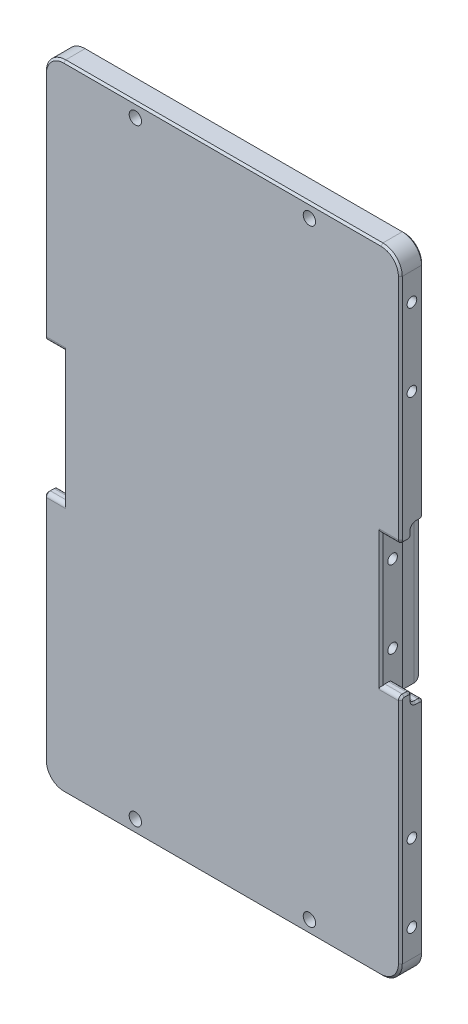
SolidWorks part; units mm, degrees
material "6061 合金"
ref_plane "前视基准面" through (0, 0, 0) normal (0, 0, 1) x (1, 0, 0)
ref_plane "上视基准面" through (0, 0, 0) normal (0, 1, 0) x (1, 0, 0)
ref_plane "右视基准面" through (0, 0, 0) normal (1, 0, 0) x (0, 0, -1)
other "Configuration Table"
sketch "草图1" plane through (0, 0, 0) normal (0, 0, 1) x (1, 0, 0)
  line L1 (-46, -82) -> (46, -82)
  line L2 (-46, -82) -> (-46, 82)
  line L3 (-46, 82) -> (46, 82)
  line L4 (46, -82) -> (46, 82)
  line L5 (-46, -82) -> (46, 82) construction
  line L6 (-46, 82) -> (46, -82) construction
  point P0 (0, 0)
  dimension "D1" = 92
  dimension "D2" = 164
extrude "凸台-拉伸1" add sketch "草图1" along normal mid plane 6
sketch "草图3" plane through (0, 0, 3) normal (0, 0, 1) x (1, 0, 0)
  line L0 (0, 82) -> (0, -82) construction
  line L1 (46, 82) -> (-46, 82) construction
  line L2 (-46, -82) -> (46, -82) construction
  line L8 (-46, 82) -> (-46, -82) construction
  line L9 (-41, -14) -> (-46, -14)
  line L10 (-41, -14) -> (-41, 14)
  line L15 (-41, 14) -> (-46, 14)
  line L21 (-46, -14) -> (-46, 14)
  line L22 (-43.5, 14) -> (-43.5, -14) construction
  line L27 (-41, 0) -> (-46, 0) construction
  line L28 (41, 14) -> (46, 14)
  line L29 (46, -14) -> (46, 14)
  line L30 (41, -14) -> (46, -14)
  line L47 (41, -14) -> (41, 14)
  point P6 (-43.5, 0)
  point P12 (0, 0)
  dimension "D1" = 28
  dimension "D2" = 5
sketch "草图97" plane through (-46, 0, 0) normal (-1, 0, 0) x (0, 0, 1)
  line L1 (0, -20.05) -> (-3, -20.05)
  line L2 (0, -20.05) -> (0, 20.05)
  line L3 (0, 20.05) -> (-3, 20.05)
  line L4 (-3, -20.05) -> (-3, 20.05)
  line L5 (-1.5, 20.05) -> (-1.5, -20.05) construction
  line L6 (0, 0) -> (-3, 0) construction
  line L8 (3, -17) -> (0, -17)
  line L9 (3, -17) -> (3, 17)
  line L10 (3, 17) -> (0, 17)
  line L11 (0, -17) -> (0, 17)
  line L12 (1.5, 17) -> (1.5, -18.4583) construction
  line L13 (3, 0) -> (0, 0) construction
  line L14 (-3, 82) -> (-3, -82) construction
  point P0 (-1.5, 0)
  point P6 (1.5, 0)
  line M2 (-3, 82) -> (-3, -82)
  line M4 (3, -82) -> (3, 82)
  dimension "D1" = 34
  dimension "D2" = 3
  dimension "D3" = 40.1
extrude "切除-拉伸1" cut sketch "草图97" against normal blind 5 contours L2 L3 L1 M2 | L10 L2 L8 M4
sketch "草图98" plane through (-41, 0, 0) normal (-1, 0, 0) x (0, 0, 1)
  line L0 (0, -10) -> (0, 10)
  line L1 (-3, 0) -> (0, 0)
  line L2 (-3, 20.05) -> (-3, -20.05) construction
  point P3 (0, 0)
  dimension "D1" = 20
  dimension "D3" = 3
hole_wizard "M3 螺纹孔1" positions "草图99" profile "草图100" tap size "M3" standard "GB"
sketch "草图99" plane through (-41, 0, 0) normal (-1, 0, 0) x (0, 0, 1)
  point P0 (0, 10)
  point P3 (0, -10)
sketch "草图100" plane through (-41, 10, 0) normal (0, 1, 0) x (0, 0, 1)
  line L0 (0, 0) -> (0, 7.5)
  line L1 (0, 7.5) -> (1.25, 6.7489)
  line L2 (1.25, 6.7489) -> (1.25, 0)
  line L5 (1.25, 0) -> (0, 0)
  line L10 (0, 7.5) -> (-1.25, 6.7489) construction
  line L11 (0, -6.35) -> (0, 107.95) construction
  dimension "螺纹孔钻头直径" = 2.5
  dimension "螺纹孔钻头深度" = 7.5
  dimension "导头角度" = 118
cosmetic thread "孔螺蚊线1" parameters "D1"=6, "D2"=3
cosmetic thread "孔螺蚊线2" parameters "D1"=6, "D2"=3
mirror "镜向1" about plane through (0, 0, 0) normal (1, 0, 0) of "M3 螺纹孔1", "切除-拉伸1"
sketch "草图101" plane through (0, 0, 3) normal (0, 0, -1) x (-1, 0, 0)
  line L0 (-19.2, 0) -> (19.2, 0)
  point P4 (0, 0)
  dimension "D1" = 38.4
hole_wizard "M4 六角凹锥坑螺钉的锥形沉头孔1" [suppressed] positions "草图101" profile "草图103" countersink size "M4" standard "ISO"
sketch "草图103" plane through (-19.2, 0, 3) normal (1, 0, 0) x (0, -1, 0)
  line L0 (0, 0) -> (0, 7.5)
  line L1 (0, 7.5) -> (2.25, 6.1481)
  line L2 (2.25, 6.1481) -> (2.25, 2.23)
  line L3 (2.25, 2.23) -> (4.48, 0)
  line L5 (4.48, 0) -> (0, 0)
  line L6 (-2.25, 2.23) -> (-4.48, 0) construction
  line L10 (0, 7.5) -> (-2.25, 6.1481) construction
  line L11 (0, -6.35) -> (0, 107.95) construction
  dimension "孔直径" = 4.5
  dimension "孔深度" = 7.5
  dimension "近端锥形沉头孔直径" = 8.96
  dimension "近端锥形沉头孔角度" = 90
  dimension "导头角度" = 118
sketch "草图104" plane through (0, 0, -3) normal (0, 0, 1) x (1, 0, 0)
  line L1 (-18, -16) -> (18, -16)
  line L2 (-18, -16) -> (-18, 16)
  line L3 (-18, 16) -> (18, 16)
  line L4 (18, -16) -> (18, 16)
  line L5 (0, 16) -> (0, -16) construction
  line L6 (-18, 0) -> (18, 0) construction
  point P0 (0, 0)
  dimension "D1" = 32
  dimension "D2" = 36
hole_wizard "Ø3.0mm 暗销孔1" [suppressed] positions "草图104" profile "草图106" hole size "Ø3.0" standard "ISO"
sketch "草图106" plane through (18, -16, -3) normal (1, 0, 0) x (0, 1, 0)
  line L0 (0, 0) -> (0, 4.4013)
  line L1 (0, 4.4013) -> (1.5, 3.5)
  line L2 (1.5, 3.5) -> (1.5, 0)
  line L5 (1.5, 0) -> (0, 0)
  line L10 (0, 4.4013) -> (-1.5, 3.5) construction
  line L11 (0, -6.35) -> (0, 107.95) construction
  dimension "孔直径" = 3
  dimension "孔深度" = 3.5
  dimension "导头角度" = 118
sketch "草图107" plane through (0, 0, 3) normal (0, 0, 1) x (1, 0, 0)
  line L0 (-7.5, 0) -> (7.5, 0)
  point P3 (0, 0)
  dimension "D1" = 15
hole_wizard "M4 螺纹孔1" [suppressed] positions "草图107" profile "草图109" tap size "M4" standard "ISO"
sketch "草图109" plane through (7.5, 0, 3) normal (1, 0, 0) x (0, -1, 0)
  line L0 (0, 0) -> (0, 10.1)
  line L1 (0, 10.1) -> (1.65, 9.1086)
  line L2 (1.65, 9.1086) -> (1.65, 0)
  line L5 (1.65, 0) -> (0, 0)
  line L10 (0, 10.1) -> (-1.65, 9.1086) construction
  line L11 (0, -6.35) -> (0, 107.95) construction
  dimension "螺纹孔钻头直径" = 3.3
  dimension "螺纹孔钻头深度" = 10.1
  dimension "导头角度" = 118
cosmetic thread "孔螺蚊线3" [suppressed] parameters "D1"=8, "D2"=4
cosmetic thread "孔螺蚊线4" [suppressed] parameters "D1"=8, "D2"=4
pattern_linear "阵列(线性)1" [suppressed] count 5 spacing 15 count 5 spacing 15
sketch "草图110" plane through (0, 0, 3) normal (0, 0, 1) x (1, 0, 0)
  line L0 (-46, 82) -> (-46, 17) construction
  line L1 (-4.25, -75) -> (4.25, -75) construction
  line L2 (-4.25, -75) -> (-4.25, 75) construction
  line L3 (-4.25, 75) -> (4.25, 75) construction
  line L4 (4.25, -75) -> (4.25, 75) construction
  line L5 (0, 75) -> (0, -75) construction
  line L6 (-4.25, 0) -> (4.25, 0) construction
  line L7 (-41, 75) -> (-11.75, 75)
  line L8 (-41, 75) -> (-41, 25)
  line L9 (-41, 25) -> (-11.75, 25)
  line L10 (-11.75, 75) -> (-11.75, 25)
  line L11 (-41, 75) -> (-11.75, 25) construction
  line L12 (-41, 25) -> (-11.75, 75) construction
  line L13 (46, 82) -> (-46, 82) construction
  line L14 (-91.2198, 0) -> (74.6821, 0) construction
  line L15 (41, 25) -> (11.75, 25)
  line L16 (11.75, 75) -> (11.75, 25)
  line L17 (41, 75) -> (11.75, 75)
  line L18 (41, 75) -> (41, 25)
  line L19 (41, -75) -> (41, -25)
  line L20 (41, -75) -> (11.75, -75)
  line L21 (11.75, -75) -> (11.75, -25)
  line L22 (41, -25) -> (11.75, -25)
  line L23 (-41, -25) -> (-11.75, -25)
  line L24 (-11.75, -75) -> (-11.75, -25)
  line L25 (-41, -75) -> (-11.75, -75)
  line L26 (-41, -75) -> (-41, -25)
  line L27 (32, -18) -> (24.25, -18)
  line L28 (-32, 18) -> (-24.25, 18)
  line L29 (-32, 18) -> (-32, -18)
  line L30 (-32, -18) -> (-24.25, -18)
  line L31 (-24.25, 18) -> (-24.25, -18)
  line L32 (-28.125, -18) -> (-28.125, 18) construction
  line L33 (-32, 0) -> (-24.25, 0) construction
  line L34 (24.25, 18) -> (24.25, -18)
  line L35 (32, 18) -> (24.25, 18)
  line L36 (32, 18) -> (32, -18)
  point P0 (0, 0)
  point P11 (-26.375, 50)
  point P30 (-28.125, 0)
  dimension "D1" = 8.5
  dimension "D2" = 7
  dimension "D3" = 5
  dimension "D4" = 7
  dimension "D5" = 7.5
  dimension "D6" = 25
  dimension "D7" = 7
  dimension "D8" = 32
  dimension "D9" = 20
extrude "切除-拉伸2" [suppressed] cut sketch "草图110" against normal blind 57
sketch "草图112" plane through (-46, 0, 0) normal (-1, 0, 0) x (0, 0, 1)
  line L0 (0, 70) -> (0, -70)
  line L1 (0, 50) -> (0, -50)
  point P1 (0, -70)
  point P2 (0, 70)
  point P7 (0, -50)
  point P20 (0, 50)
  point P25 (0, 0)
  dimension "D1" = 140
  dimension "D2" = 100
sketch "草图111" plane through (0, 0, -3) normal (0, 0, -1) x (-1, 0, 0)
  line L1 (-7.9, -49) -> (7.9, -49)
  line L2 (-7.9, -49) -> (-7.9, -57)
  line L3 (-7.9, -57) -> (7.9, -57)
  line L4 (7.9, -49) -> (7.9, -57)
  line L5 (0, -57) -> (0, -49) construction
  line L6 (-7.9, -53) -> (7.9, -53) construction
  point P0 (0, -53)
  point P4 (0, 0)
  dimension "D1" = 8
  dimension "D2" = 15.8
  dimension "D3" = 53
extrude "切除-拉伸3" [suppressed] cut sketch "草图111" against normal blind 10
fillet "圆角4" [suppressed] radius 0.5
fillet "圆角6" [suppressed] radius 1
fillet "圆角7" [suppressed] radius 2
hole_wizard "M3 螺纹孔2" positions "草图112" profile "草图113" tap size "M3" standard "ISO"
sketch "草图113" plane through (-46, -70, 0) normal (0, 1, 0) x (0, 0, 1)
  line L0 (0, 0) -> (0, 7.5)
  line L1 (0, 7.5) -> (1.25, 6.7489)
  line L2 (1.25, 6.7489) -> (1.25, 0)
  line L5 (1.25, 0) -> (0, 0)
  line L10 (0, 7.5) -> (-1.25, 6.7489) construction
  line L11 (0, -6.35) -> (0, 107.95) construction
  dimension "螺纹孔钻头直径" = 2.5
  dimension "螺纹孔钻头深度" = 7.5
  dimension "导头角度" = 118
cosmetic thread "孔螺蚊线5" parameters "D1"=6, "D2"=3
cosmetic thread "孔螺蚊线6" parameters "D1"=6, "D2"=3
cosmetic thread "孔螺蚊线8" parameters "D1"=6, "D2"=3
cosmetic thread "孔螺蚊线9" parameters "D1"=6, "D2"=3
mirror "镜向2" about plane through (0, 0, 0) normal (1, 0, 0) of "M3 螺纹孔2"
fillet "圆角1" [suppressed] radius 3
fillet "圆角2" [suppressed] radius 2
fillet "圆角3" radius 5 4 edges at (46, -82, 0) (-46, -82, 0) (-46, 82, 0) (46, 82, 0)
fillet "圆角5" radius 1 16 edges at (-43.5, -17, 0) (-43.5, -20.05, 0) (-43.5, -20.05, -3) (-43.5, 20.05, -3) (-43.5, 20.05, 0) (-43.5, 17, 0) (-43.5, 17, 3) (-43.5, -17, 3) (43.5, -20.05, 0) (43.5, -17, 0) (43.5, -17, 3) (43.5, 17, 3) (43.5, 17, 0) (43.5, 20.05, 0) (43.5, 20.05, -3) (43.5, -20.05, -3)
sketch "草图114" [suppressed] plane through (0, 0, -3) normal (0, 0, -1) x (-1, 0, 0)
  line L1 (-41, -68.5) -> (-11.75, -68.5)
  line L2 (-41, -68.5) -> (-41, -88.5)
  line L3 (-41, -88.5) -> (-11.75, -88.5)
  line L4 (-11.75, -68.5) -> (-11.75, -88.5)
  line L5 (-41, -68.5) -> (-11.75, -88.5) construction
  line L6 (-41, -88.5) -> (-11.75, -68.5) construction
  line L11 (-11.75, -75) -> (-11.75, -25) construction
  line L12 (-41, -25) -> (-41, -75) construction
  line L13 (-26.375, -75) -> (-26.375, -82) construction
  line L14 (-41, -75) -> (-11.75, -75) construction
  line L15 (41, -82) -> (-41, -82) construction
  point P4 (-26.375, -78.5)
  dimension "D1" = 20
extrude "切除-拉伸4" [suppressed] cut sketch "草图114" against normal blind 2
sketch "草图115" [suppressed] plane through (0, 0, -1) normal (0, 0, -1) x (-1, 0, 0)
  line L0 (-41, -82) -> (-11.75, -82) construction
  point P0 (-22.5, -78.5)
  point P1 (0, 0)
  dimension "D1" = 22.5
  dimension "D2" = 3.5
hole_wizard "M3 螺纹孔3" [suppressed] positions "草图115" profile "草图116" tap size "M3" standard "ISO"
sketch "草图116" plane through (22.5, -78.5, -1) normal (1, 0, 0) x (0, 1, 0)
  line L0 (0, 0) -> (0, 7.5)
  line L1 (0, 7.5) -> (1.25, 6.7489)
  line L2 (1.25, 6.7489) -> (1.25, 0)
  line L5 (1.25, 0) -> (0, 0)
  line L10 (0, 7.5) -> (-1.25, 6.7489) construction
  line L11 (0, -6.35) -> (0, 107.95) construction
  dimension "螺纹孔钻头直径" = 2.5
  dimension "螺纹孔钻头深度" = 7.5
  dimension "导头角度" = 118
cosmetic thread "孔螺蚊线10" [suppressed] parameters "D1"=6, "D2"=3
cosmetic thread "孔螺纹线1" [suppressed] parameters "D1"=6, "D2"=3
mirror "镜向6" [suppressed] about plane through (0, 0, 0) normal (0, 1, 0)
fillet "圆角8" [suppressed] radius 1
sketch "草图117" plane through (0, 0, -3) normal (0, 0, -1) x (-1, 0, 0)
  line L1 (-12.4, 12.4) -> (12.4, 12.4)
  line L2 (-12.4, 12.4) -> (-12.4, -12.4)
  line L3 (-12.4, -12.4) -> (12.4, -12.4)
  line L4 (12.4, 12.4) -> (12.4, -12.4)
  line L5 (0, -12.4) -> (0, 12.4) construction
  line L6 (-12.4, 0) -> (12.4, 0) construction
  point P0 (0, 0)
  dimension "D1" = 24.8
extrude "切除-拉伸5" [suppressed] cut sketch "草图117" against normal blind 10
fillet "圆角9" [suppressed] radius 1
chamfer "倒角1" [suppressed] distance 0.5 angle 45
chamfer "倒角2" distance 0.5 angle 45 52 edges at (-41, 0, 3) (-46, 47.5, 3) (-44.5355, 80.5355, 3) (0, 82, 3) (44.5355, 80.5355, 3) (46, 47.5, 3) (41, 0, 3) (-46, -47.5, 3) (-44.5355, -80.5355, 3) (0, -82, 3) (44.5355, -80.5355, 3) (46, -47.5, 3) (41, 0, -3) (46, 17.2929, 2.7071) (-46, 17.2929, 2.7071) (46, 17, 1.5) (-46, 17, 1.5) (46, 17.2929, 0.2929) (-46, 17.2929, 0.2929) (46, 18.525, 0) (-46, -18.525, 0) (46, 19.7571, -0.2929) (-46, 19.7571, -0.2929) (46, 20.05, -1.5) (-46, 20.05, -1.5) (46, 20.3429, -2.7071) (-46, 20.3429, -2.7071) (46, 49.025, -3) (44.5355, 80.5355, -3) (0, 82, -3) (-44.5355, 80.5355, -3) (-46, 49.025, -3) (-41, 0, -3) (46, -17.2929, 2.7071) (-46, -17.2929, 2.7071) (46, -17, 1.5) (-46, -17, 1.5) (46, -17.2929, 0.2929) (-46, -17.2929, 0.2929) (46, -18.525, 0) (-46, 18.525, 0) (46, -19.7571, -0.2929) (-46, -19.7571, -0.2929) (46, -20.05, -1.5) (-46, -20.05, -1.5) (46, -20.3429, -2.7071) (-46, -20.3429, -2.7071) (46, -49.025, -3) (-46, -49.025, -3) (-44.5355, -80.5355, -3) (0, -82, -3) (44.5355, -80.5355, -3)
sketch "草图119" plane through (0, 0, -3) normal (0, 0, -1) x (-1, 0, 0)
  line L0 (-41, 0) -> (41, 0) construction
  line L1 (-41, 21.05) -> (-41, -21.05) construction
  line L2 (41, 21.05) -> (41, -21.05) construction
  line L3 (0, 82) -> (0, -82) construction
  line L4 (-41, 82) -> (41, 82) construction
  line L5 (41, -82) -> (-41, -82) construction
  circle A1 centre (22.5, 78.5) radius 1.6
  circle A4 centre (-22.5, 78.5) radius 1.6
  circle A5 centre (22.5, -78.5) radius 1.6
  circle A6 centre (-22.5, -78.5) radius 1.6
  dimension "D3" = 3.2
  dimension "D1" = 22.5
  dimension "D2" = 3.5
extrude "切除-拉伸6" cut sketch "草图119" against normal through all
sketch "草图120" plane through (0, 0, -3) normal (0, 0, -1) x (-1, 0, 0)
  line L12 (-40.5, 0) -> (40.5, 0) construction
  line L13 (-40.5, 21.05) -> (-40.5, -21.05) construction
  line L14 (40.5, -21.05) -> (40.5, 21.05) construction
  line L15 (-26.5, 21.05) -> (26.5, 21.05)
  line L16 (30.5, 25.05) -> (30.5, 31.05)
  line L17 (30.5, -31.05) -> (30.5, -25.05)
  line L18 (26.5, -21.05) -> (-26.5, -21.05)
  line L19 (-30.5, -25.05) -> (-30.5, -31.05)
  line L20 (-30.5, 25.05) -> (-30.5, 31.05)
  line L24 (-30.5, 31.05) -> (-30.5, -31.05)
  line L25 (-30.5, -31.05) -> (-35.5, -31.05)
  line L26 (-35.5, -31.05) -> (-35.5, -71.5)
  line L27 (-35.5, -71.5) -> (35.5, -71.5)
  line L28 (35.5, -71.5) -> (35.5, -31.05)
  line L29 (35.5, -31.05) -> (30.5, -31.05)
  line L30 (30.5, -31.05) -> (30.5, 31.05)
  line L31 (30.5, 31.05) -> (35.5, 31.05)
  line L32 (35.5, 31.05) -> (35.5, 71.5)
  line L33 (35.5, 71.5) -> (-35.5, 71.5)
  line L34 (-35.5, 71.5) -> (-35.5, 31.05)
  line L35 (-35.5, 31.05) -> (-30.5, 31.05)
  line L36 (-30.5, 31.05) -> (-30.5, -31.05) construction
  line L37 (-30.5, -31.05) -> (-31.5, -31.05)
  line L38 (-35.5, -35.05) -> (-35.5, -67.5)
  line L39 (-31.5, -71.5) -> (31.5, -71.5)
  line L40 (35.5, -67.5) -> (35.5, -35.05)
  line L41 (31.5, -31.05) -> (30.5, -31.05)
  line L42 (30.5, -31.05) -> (30.5, 31.05) construction
  line L43 (30.5, 31.05) -> (31.5, 31.05)
  line L44 (35.5, 35.05) -> (35.5, 67.5)
  line L45 (31.5, 71.5) -> (-31.5, 71.5)
  line L46 (-35.5, 67.5) -> (-35.5, 35.05)
  line L47 (-31.5, 31.05) -> (-30.5, 31.05)
  arc A4 (31.5, -71.5) -> (35.5, -67.5) centre (31.5, -67.5) ccw
  arc A5 (-35.5, -67.5) -> (-31.5, -71.5) centre (-31.5, -67.5) ccw
  arc A6 (-31.5, -31.05) -> (-35.5, -35.05) centre (-31.5, -35.05) ccw
  arc A7 (35.5, -35.05) -> (31.5, -31.05) centre (31.5, -35.05) ccw
  arc A8 (30.5, -25.05) -> (26.5, -21.05) centre (26.5, -25.05) ccw
  arc A9 (-26.5, -21.05) -> (-30.5, -25.05) centre (-26.5, -25.05) ccw
  arc A10 (-26.5, 21.05) -> (-30.5, 25.05) centre (-26.5, 25.05) cw
  arc A11 (26.5, 21.05) -> (30.5, 25.05) centre (26.5, 25.05) ccw
  arc A12 (31.5, 31.05) -> (35.5, 35.05) centre (31.5, 35.05) ccw
  arc A13 (-35.5, 35.05) -> (-31.5, 31.05) centre (-31.5, 35.05) ccw
  arc A14 (35.5, 67.5) -> (31.5, 71.5) centre (31.5, 67.5) ccw
  arc A15 (-31.5, 71.5) -> (-35.5, 67.5) centre (-31.5, 67.5) ccw
  point P28 (30.5, -21.05)
  point P32 (-30.5, -21.05)
  point P37 (-30.5, 21.05)
  point P43 (30.5, 21.05)
  dimension "D4" = 4
  dimension "D2" = 21.05
  dimension "D3" = 21.05
  dimension "D1" = 10
extrude "切除-拉伸7" cut sketch "草图120" against normal blind 3
sketch "草图121" plane through (0, 0, -3) normal (0, 0, -1) x (-1, 0, 0)
chamfer "倒角3" distance 3 angle 45 28 edges at (34.3284, 32.2216, 0) (35.5, 51.275, 0) (34.3284, 70.3284, 0) (0, 71.5, 0) (-34.3284, 70.3284, 0) (-35.5, 51.275, 0) (-34.3284, 32.2216, 0) (-31, 31.05, 0) (-30.5, 28.05, 0) (-29.3284, 22.2216, 0) (0, 21.05, 0) (29.3284, 22.2216, 0) (30.5, 28.05, 0) (31, 31.05, 0) (0, -71.5, 0) (34.3284, -70.3284, 0) (35.5, -51.275, 0) (34.3284, -32.2216, 0) (31, -31.05, 0) (30.5, -28.05, 0) (29.3284, -22.2216, 0) (0, -21.05, 0) (-29.3284, -22.2216, 0) (-30.5, -28.05, 0) (-31, -31.05, 0) (-34.3284, -32.2216, 0) (-35.5, -51.275, 0) (-34.3284, -70.3284, 0)
sketch "草图122" plane through (0, 0, -3) normal (0, 0, -1) x (-1, 0, 0)
  line L21 (-40.5, 21.05) -> (40.5, 21.05)
  line L22 (-40.5, 21.05) -> (-40.5, -21.05)
  line L23 (-40.5, -21.05) -> (40.5, -21.05)
  line L24 (40.5, 21.05) -> (40.5, -21.05)
extrude "凸台-拉伸3" add sketch "草图122" along normal blind 6
fillet "圆角11" radius 3 4 edges at (0, 21.05, -9) (-40.5, 0, -9) (0, -21.05, -9) (40.5, 0, -9)
sketch "草图123" plane through (0, 0, -9) normal (0, 0, -1) x (-1, 0, 0)
  line L8 (31.5, -12.05) -> (31.5, 12.05)
  line L9 (31.5, 12.05) -> (-31.5, 12.05)
  line L10 (-31.5, 12.05) -> (-31.5, -12.05)
  line L11 (-31.5, -12.05) -> (31.5, -12.05)
  line L12 (31.5, -12.05) -> (31.5, 12.05)
  line L13 (31.5, 12.05) -> (-31.5, 12.05)
  line L14 (-31.5, 12.05) -> (-31.5, -12.05)
  line L15 (-31.5, -12.05) -> (31.5, -12.05)
  dimension "D1" = 6
extrude "切除-拉伸8" cut sketch "草图123" against normal blind 6
fillet "圆角12" radius 3 4 edges at (31.5, -12.05, -6) (31.5, 12.05, -6) (-31.5, -12.05, -6) (-31.5, 12.05, -6)
